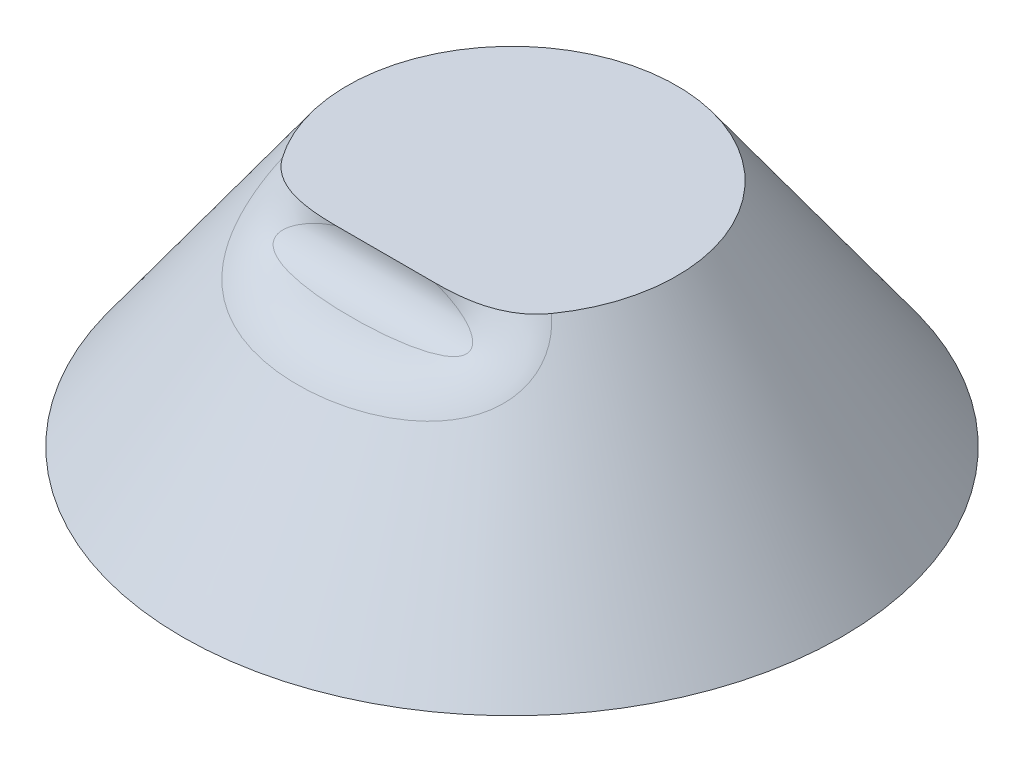
SolidWorks part; units mm, degrees
ref_plane "Płaszczyzna przednia" through (0, 0, 0) normal (0, 0, 1) x (1, 0, 0)
ref_plane "Płaszczyzna górna" through (0, 0, 0) normal (0, 1, 0) x (1, 0, 0)
ref_plane "Płaszczyzna prawa" through (0, 0, 0) normal (1, 0, 0) x (0, 0, -1)
sketch "Szkic6" plane through (0, 0, 0) normal (1, 0, 0) x (0, 0, -1)
  line L0 (0, 0) -> (42.9807, 0)
  line L1 (42.9807, 0) -> (21.4904, 30)
  line L2 (21.4904, 30) -> (0, 30)
  line L3 (0, 30) -> (0, 0)
revolve "Obrót2" add sketch "Szkic6" angle 360 about L3
sketch "Szkic8" plane through (0, 0, 0) normal (1, 0, 0) x (0, 0, -1)
  circle A0 centre (-21.4904, 30) radius 4.9549
extrude "Wytnij-wyciągnięcie1" cut sketch "Szkic8" against normal blind 30 and the other way blind 30 contours A0
fillet "Zaokrąglenie1" radius 10 1 edges at (0.2119, 25.9715, 24.3753)
